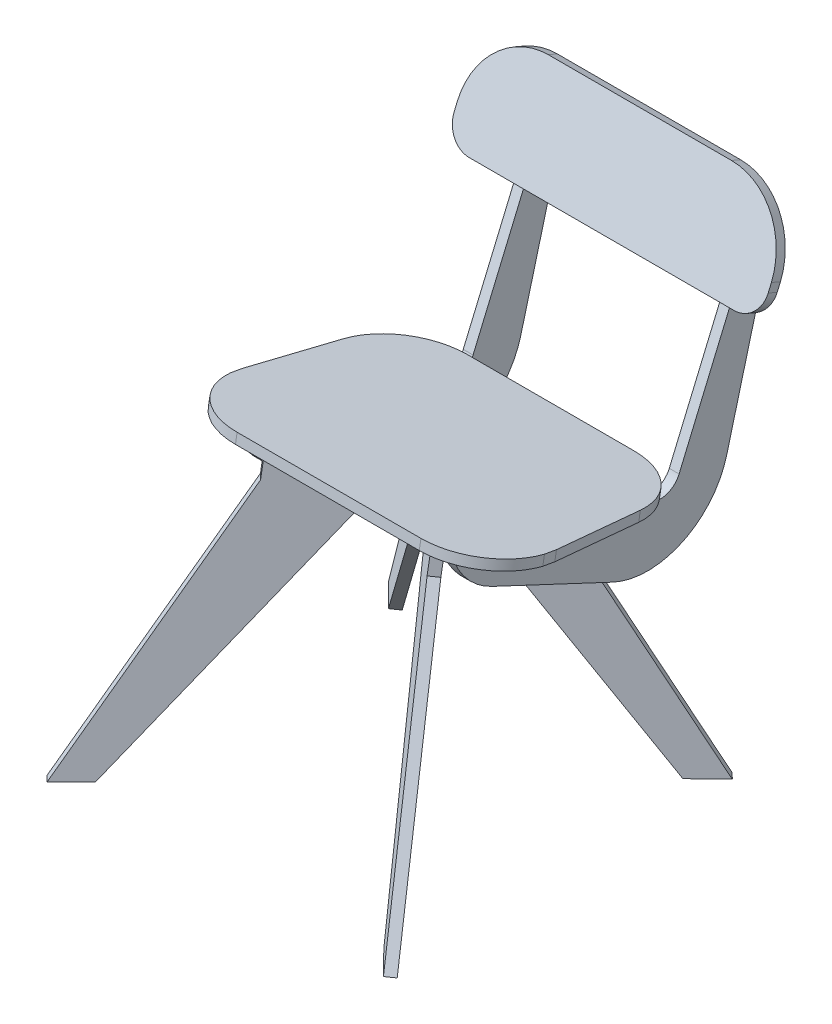
SolidWorks part; units mm, degrees
ref_plane "Front Plane" through (0, 0, 0) normal (0, 0, 1) x (1, 0, 0)
ref_plane "Top Plane" through (0, 0, 0) normal (0, 1, 0) x (1, 0, 0)
ref_plane "Right Plane" through (0, 0, 0) normal (1, 0, 0) x (0, 0, -1)
sketch "Sketch1" plane through (0, 0, 0) normal (0, 1, 0) x (1, 0, 0)
  line L2 (0, -17.5) -> (11.2397, -17.5)
  line L3 (0, -17.5) -> (-11.2397, -17.5)
  line L5 (-10.1943, 10) -> (10.1943, 10)
  line L7 (19.2069, -8.7757) -> (18.1614, 2.7243)
  line L8 (-19.2069, -8.7757) -> (-18.1614, 2.7243)
  arc A0 (10.1943, 10) -> (18.1614, 2.7243) centre (10.1943, 2) cw
  arc A1 (19.2069, -8.7757) -> (11.2397, -17.5) centre (11.2397, -9.5) cw
  arc A2 (-19.2069, -8.7757) -> (-11.2397, -17.5) centre (-11.2397, -9.5) ccw
  arc A3 (-10.1943, 10) -> (-18.1614, 2.7243) centre (-10.1943, 2) ccw
  dimension "D1" = 8
sketch "Sketch2" plane through (0, 0, 0) normal (1, 0, 0) x (0, 0, -1)
  line L0 (0, 0) -> (-270.8221, 47.7532)
  line L1 (0, 0) -> (85.9608, 202.5111) construction
  line L2 (-45.6761, 0) -> (45.6761, 0) construction
  line L3 (109.4047, 257.7414) -> (62.517, 147.2808)
  line L4 (-2.0838, -11.8177) -> (-272.9059, 35.9356)
  line L5 (120.4508, 253.0526) -> (73.563, 142.592)
  line L6 (-272.9059, 35.9356) -> (-270.8221, 47.7532)
  line L7 (-2.0838, -11.8177) -> (0, 0)
  line L8 (73.563, 142.592) -> (62.517, 147.2808)
  line L9 (120.4508, 253.0526) -> (109.4047, 257.7414)
  point P7 (0, 0)
  point P10 (85.9608, 202.5111)
  dimension "D1" = 275
  dimension "D2" = 10
  dimension "D3" = 220
  dimension "D4" = 120
  dimension "D7" = 103
  dimension "D5" = 12
  dimension "D6" = 12
extrude "Boss-Extrude1" add sketch "Sketch2" along normal blind 192.05 and the other way blind 192.05
sketch "Sketch3" plane through (0, 0, 0) normal (0, 0.9848, -0.1736) x (1, 0, 0)
  line L0 (0, -275) -> (112.3974, -275)
  line L1 (0, -275) -> (-112.3974, -275)
  line L2 (-101.9428, 0) -> (101.9428, 0)
  line L3 (192.0688, -187.7571) -> (181.6143, -72.7571)
  line L4 (-192.0688, -187.7571) -> (-181.6143, -72.7571)
  arc A0 (101.9428, 0) -> (181.6143, -72.7571) centre (101.9428, -80) cw
  arc A1 (192.0688, -187.7571) -> (112.3974, -275) centre (112.3974, -195) cw
  arc A2 (-192.0688, -187.7571) -> (-112.3974, -275) centre (-112.3974, -195) ccw
  arc A3 (-101.9428, 0) -> (-181.6143, -72.7571) centre (-101.9428, -80) ccw
extrude "Cut-Extrude1" cut sketch "Sketch3" against normal blind 12 flip side to cut
sketch "Sketch4" plane through (0, 0, 0) normal (0, 0.3907, 0.9205) x (1, 0, 0)
  line L0 (192.05, 280) -> (192.05, 160) construction
  line L1 (-112.05, 280) -> (112.05, 280)
  line L2 (-192.05, 200) -> (-192.05, 190)
  line L3 (-162.05, 160) -> (162.05, 160)
  line L4 (192.05, 200) -> (192.05, 190)
  arc A0 (192.05, 200) -> (112.05, 280) centre (112.05, 200) ccw
  arc A1 (-112.05, 280) -> (-192.05, 200) centre (-112.05, 200) ccw
  arc A2 (192.05, 190) -> (162.05, 160) centre (162.05, 190) cw
  arc A3 (-162.05, 160) -> (-192.05, 190) centre (-162.05, 190) cw
  point P11 (-192.05, 280)
  point P14 (192.05, 160)
  dimension "D1" = 80
  dimension "D2" = 30
extrude "Cut-Extrude2" cut sketch "Sketch4" against normal blind 12 flip side to cut
sketch "Sketch6" plane through (0, 0, 0) normal (1, 0, 0) x (0, 0, -1)
  line L4 (89.1923, 179.4122) -> (120.4508, 253.0526) construction
  line L6 (-253.2098, 32.4626) -> (-137.4948, 12.0589)
  line L7 (-272.9059, 35.9356) -> (-201.4552, 23.3369) construction
  line L8 (91.9731, 134.7774) -> (25.3016, -22.2909)
  line L11 (-55.6688, -96.3871) -> (-203.3734, -27.0621)
  line L14 (83.4899, -31.45) -> (131.798, 151.0571)
  line L15 (81.3777, 161.0021) -> (112.6362, 234.6425)
  line L17 (-73.7356, 0.8165) -> (-2.0838, -11.8177) construction
  line L18 (-21.7799, -8.3447) -> (-137.4948, 12.0589)
  arc A7 (81.3777, 161.0021) -> (91.9731, 134.7774) centre (73.563, 142.592) cw
  arc A8 (131.798, 151.0571) -> (112.6362, 234.6425) centre (42.7404, 174.6299) ccw
  arc A9 (-253.2098, 32.4626) -> (-203.3734, -27.0621) centre (-164.2317, 56.3337) ccw
  arc A11 (-55.6688, -96.3871) -> (83.4899, -31.45) centre (-13.181, -5.8621) ccw
  arc A13 (-21.7799, -8.3447) -> (25.3016, -22.2909) centre (2.5553, -12.6357) ccw
  point P0 (107.5102, 171.3804)
  point P5 (25.3016, -22.2909)
  dimension "D2" = 8.174
extrude "Boss-Extrude4" add sketch "Sketch6" along normal blind 12 from offset 120
mirror "Mirror1" about plane through (0, 0, 0) normal (1, 0, 0) of "Boss-Extrude4"
sketch "Sketch25" plane through (0, -11.8177, 2.0838) normal (0, -0.9848, 0.1736) x (1, 0, 0)
  line L0 (0, 0) -> (0, 275)
  line L1 (-101.9428, 0) -> (101.9428, 0) construction
  line L2 (-112.3974, 275) -> (112.3974, 275) construction
  line L3 (0, 137.5) -> (-120, 137.5)
  line L4 (-120, 20) -> (-120, 255) construction
  line L5 (-120, 137.5) -> (-120, 257.5)
  line L6 (0, 137.5) -> (120, 137.5)
  line L7 (120, 20) -> (120, 255) construction
  line L8 (120, 137.5) -> (120, 17.5)
  line L9 (120, 195.5844) -> (120, 38.0857) construction
  line L10 (-120, 257.5) -> (120, 17.5)
ref_plane "Plane6" through (68.75, 11.9383, 67.7055) normal (0.7071, 0.1228, 0.6964) x (0.7071, -0.1228, -0.6964)
ref_plane "Plane4" through (0, -300, 0) normal (0, 1, 0) x (1, 0, 0)
sketch "Sketch27" plane through (68.75, 11.9383, 67.7055) normal (0.7071, 0.1228, 0.6964) x (0.7071, -0.1228, -0.6964)
  line L0 (-211.6311, -343.8851) -> (-253.4341, -349.0972) construction
  line L1 (52.7728, -107.5379) -> (193.944, -293.3172)
  line L2 (52.7728, -107.5379) -> (52.7728, -12)
  line L3 (-253.4341, -349.0972) -> (-247.2272, -50.1295) construction
  line L4 (-247.2272, -50.1295) -> (-247.2272, -12)
  line L5 (52.7728, -12) -> (-247.2272, -12)
  line L6 (151.4632, -297.8657) -> (-40.7003, -88.5026)
  line L7 (151.4632, -297.8657) -> (193.944, -293.3172)
  line L8 (-158.449, -65.97) -> (-40.7003, -88.5026)
  line L9 (-158.449, -65.97) -> (-211.6311, -343.8851) construction
  line L10 (193.944, -293.3172) -> (-253.4341, -349.0972) construction
  line L11 (-253.4341, -349.0972) -> (-411.5788, -368.815) construction
  line L15 (-394.3073, -366.6616) -> (-352.63, -361.4652)
  line L16 (-394.3073, -366.6616) -> (-247.2272, -50.1295)
  line L17 (-352.63, -361.4652) -> (-158.449, -65.97)
extrude "Boss-Extrude10" add sketch "Sketch27" along normal blind 6 and the other way blind 6
mirror "Mirror3" about plane through (0, 0, 0) normal (1, 0, 0) of "Boss-Extrude10"
sketch "Sketch7" plane through (0, -11.8177, 2.0838) normal (0, -0.9848, 0.1736) x (1, 0, 0)
  line L18 (4.2426, 141.7426) -> (110.3087, 35.6766)
  line L19 (4.2426, 141.7426) -> (-101.8234, 247.8087)
  line L20 (-4.2426, 133.2574) -> (101.8234, 27.1913)
  line L21 (-4.2426, 133.2574) -> (-110.3087, 239.3234)
  line L22 (-110.3087, 239.3234) -> (-101.8234, 247.8087)
  line L23 (101.8234, 27.1913) -> (110.3087, 35.6766)
extrude "Boss-Extrude8" [suppressed] add sketch "Sketch7" along normal blind 200
ref_plane "Plane5" [suppressed] through (68.75, 11.9383, 67.7055) normal (0.7071, 0.1228, 0.6964) x (0.6861, 0.1191, -0.7177)
sketch "Sketch18" plane through (0, -100.3986, 47.122) normal (0, -0.9053, 0.4249) x (1, 0, 0)
  circle A0 centre (0, 0) radius 298.5548
extrude "Cut-Extrude5" [suppressed] cut sketch "Sketch18" along normal blind 238
sketch "Sketch19" [suppressed] plane through (64.5074, 11.2016, 63.5273) normal (-0.7071, -0.1228, -0.6964) x (-0.6861, -0.1191, 0.7177)
  line L0 (-25.1855, -117.1113) -> (-135.105, -373.2176)
  line L5 (252.0105, 11.1778) -> (337.9126, -305.1843)
  line L6 (337.9126, -305.1843) -> (-135.105, -373.2176)
  line L7 (-25.1855, -117.1113) -> (-29.983, -97.8724)
  line L8 (-25.1855, -117.1113) -> (-48.3013, -24.4121) construction
  line L9 (-29.983, -97.8724) -> (249.4577, 21.415)
  line L10 (252.0105, 11.1778) -> (242.7849, 48.1743) construction
  line L11 (249.4577, 21.415) -> (252.0105, 11.1778)
extrude "Boss-Extrude9" [suppressed] add sketch "Sketch19" against normal blind 12
sketch "Sketch20" plane through (0, -300, 0) normal (0, 1, 0) x (1, 0, 0)
  circle A0 centre (0, 0) radius 368.7738
extrude "Cut-Extrude6" [suppressed] cut sketch "Sketch20" against normal blind 95
sketch "Sketch21" plane through (0, 0, 0) normal (1, 0, 0) x (0, 0, -1)
  line L5 (-189.4993, -33.5739) -> (-111.4161, -70.2222)
  line L9 (-7.7577, -314.613) -> (-111.4161, -70.2222)
  line L11 (-7.7577, -314.613) -> (-279.5337, -314.613)
  line L16 (-279.5337, -314.613) -> (-189.4993, -33.5739)
extrude "Cut-Extrude8" [suppressed] cut sketch "Sketch21" against normal blind 141 and the other way blind 207
sketch "Sketch23" [suppressed] plane through (68.75, 11.9383, 67.7055) normal (0.7071, 0.1228, 0.6964) x (0.6861, 0.1191, -0.7177)
  line L8 (25.1855, -117.1113) -> (117.212, -331.5277) construction
  line L9 (25.1855, -117.1113) -> (48.3013, -24.4121) construction
  line L10 (-330.3696, -277.4051) -> (-252.0105, 11.1778) construction
  line L11 (-252.0105, 11.1778) -> (-242.7849, 48.1743) construction
  line L12 (48.3013, -24.4121) -> (-242.7849, 48.1743) construction
  line L13 (-288.5477, -282.4623) -> (-330.3696, -277.4051)
  line L21 (25.1855, -117.1113) -> (117.212, -331.5277)
  line L22 (25.1855, -117.1113) -> (48.3013, -24.4121)
  line L23 (-330.3696, -277.4051) -> (-252.0105, 11.1778)
  line L24 (-252.0105, 11.1778) -> (-242.7849, 48.1743)
  line L25 (48.3013, -24.4121) -> (-242.7849, 48.1743)
  line L28 (74.8928, -325.6626) -> (-60.9047, -76.0253)
  line L29 (69.0711, -324.2109) -> (80.7146, -327.1144) construction
  line L30 (-55.0829, -77.477) -> (-66.7264, -74.5736) construction
  line L31 (74.8928, -325.6626) -> (117.212, -331.5277)
  line L33 (-169.7028, -25.6724) -> (-60.9047, -76.0253)
  line L34 (-169.7028, -25.6724) -> (-288.5477, -282.4623)
